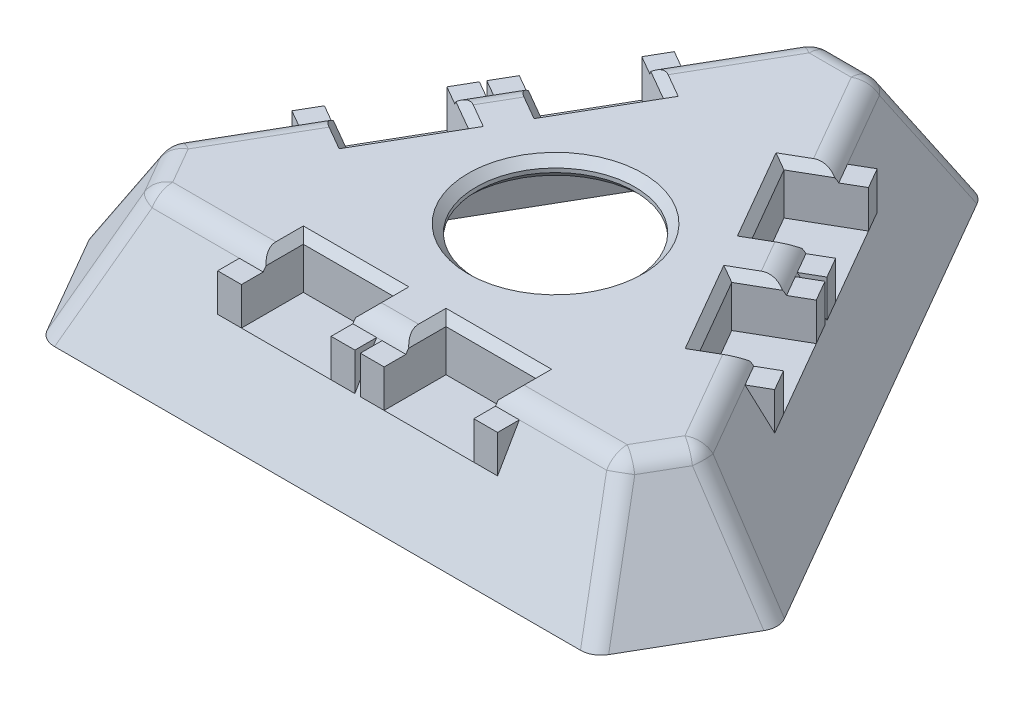
SolidWorks part; units mm, degrees
material "Epoxy, Unfilled"
ref_plane "Front Plane" through (0, 0, 0) normal (0, 0, 1) x (1, 0, 0)
ref_plane "Top Plane" through (0, 0, 0) normal (0, 1, 0) x (1, 0, 0)
ref_plane "Right Plane" through (0, 0, 0) normal (1, 0, 0) x (0, 0, -1)
sketch "Sketch1" plane through (0, 0, 0) normal (0, 1, 0) x (1, 0, 0)
  line L1 (7.32, 72.6795) -> (-7.32, 72.6795) construction
  line L5 (59.2822, -42.6788) -> (-59.2822, -42.6788) construction
  line L11 (-7.32, 72.6795) -> (-66.6024, -30.0002) construction
  line L13 (-59.2822, -42.6788) -> (-66.6024, -30.0002) construction
  line L15 (59.2822, -42.6788) -> (66.6024, -30.0002) construction
  line L16 (66.6024, -30.0002) -> (7.32, 72.6795) construction
  line L17 (69.282, -59.9993) -> (-69.2821, -59.9993)
  line L18 (-69.2821, -59.9993) -> (-86.6026, -30.0004)
  line L19 (-17.32, 90) -> (-86.6026, -30.0004)
  line L20 (17.32, 90) -> (-17.32, 90)
  line L21 (86.6025, -30.0004) -> (17.32, 90)
  line L22 (69.282, -59.9993) -> (86.6025, -30.0004)
  point P4 (0, 72.6795)
  point P6 (0, -42.6788)
  point P14 (0, 90)
  dimension "D4" = 90
  dimension "D3" = 34.64
  dimension "D1" = 138.5641
  dimension "D2" = 173.2051
  dimension "D6" = 17.3205
extrude "Boss-Extrude1" add sketch "Sketch1" along normal blind 30 draft 30
sketch "Sketch2" plane through (0, 0, 0) normal (0, -1, 0) x (1, 0, 0)
  line L10 (51.9609, 29.9993) -> (-51.9609, 29.9993)
  line L12 (51.9609, 29.9993) -> (-51.9609, 29.9993)
  line L24 (-51.9609, 29.9993) -> (0, -59.9992)
  line L25 (-51.9609, 29.9993) -> (0, -59.9992)
  line L28 (0, -59.9992) -> (51.9609, 29.9993)
  line L29 (0, -59.9992) -> (51.9609, 29.9993)
  dimension "D1" = 30
extrude "Cut-Extrude1" cut sketch "Sketch2" against normal blind 25
sketch "Sketch3" plane through (0, 0, 0) normal (0, -1, 0) x (1, 0, 0)
  line L6 (75.0555, 30.0003) -> (63.5087, 49.9993)
  line L8 (75.0555, 30.0003) -> (63.5087, 49.9993)
  line L10 (63.5087, 49.9993) -> (-63.5087, 49.9993)
  line L12 (63.5087, 49.9993) -> (-63.5087, 49.9993)
  line L14 (-63.5087, 49.9993) -> (-75.0555, 30.0003)
  line L16 (-63.5087, 49.9993) -> (-75.0555, 30.0003)
  line L24 (-75.0555, 30.0003) -> (-11.5465, -80)
  line L25 (-75.0555, 30.0003) -> (-11.5465, -80)
  line L26 (-11.5465, -80) -> (11.5465, -80)
  line L27 (-11.5465, -80) -> (11.5465, -80)
  line L28 (11.5465, -80) -> (75.0555, 30.0003)
  line L29 (11.5465, -80) -> (75.0555, 30.0003)
  dimension "D1" = 10
extrude "Cut-Extrude2" cut sketch "Sketch3" against normal offset from surface (12.5 mm away) 17.5 up to face at (0, 30, -0.0002)
ref_plane "Plane1" through (0, 0, 59.9993) normal (0, 0, 1) x (1, 0, 0)
ref_plane "Plane2" through (51.9612, 0, -29.9999) normal (0.866, 0, -0.5) x (-0.5, 0, -0.866)
ref_plane "Plane3" through (-51.9612, 0, -29.9999) normal (-0.866, 0, -0.5) x (-0.5, 0, 0.866)
sketch "Sketch7" plane through (0, 0, 59.9993) normal (0, 0, 1) x (1, 0, 0)
  line L0 (59.2822, 30) -> (66.6024, 30) construction
  line L1 (-29.2821, 30) -> (-6.6821, 30)
  line L2 (-29.2821, 30) -> (-29.2821, 17.5)
  line L3 (-29.2821, 17.5) -> (-6.6821, 17.5)
  line L4 (-6.6821, 30) -> (-6.6821, 17.5)
  line L5 (6.682, 30) -> (29.282, 30)
  line L6 (6.682, 30) -> (6.682, 17.5)
  line L7 (6.682, 17.5) -> (29.282, 17.5)
  line L8 (29.282, 30) -> (29.282, 17.5)
  dimension "D1" = 22.6
  dimension "D2" = 22.6
  dimension "D3" = 40
  dimension "D4" = 40
  dimension "D5" = 12.5
extrude "Cut-Extrude6" cut sketch "Sketch7" against normal blind 25.7036
sketch "Sketch8" plane through (-51.9612, 0, -29.9999) normal (-0.866, 0, -0.5) x (-0.5, 0, 0.866)
  line L0 (44.3419, 30) -> (51.6019, 30) construction
  line L1 (-29.2822, 30) -> (-6.6822, 30)
  line L2 (-29.2822, 30) -> (-29.2822, 17.5)
  line L3 (-29.2822, 17.5) -> (-6.6822, 17.5)
  line L4 (-6.6822, 30) -> (-6.6822, 17.5)
  line L5 (6.6825, 30) -> (29.2825, 30)
  line L6 (6.6825, 30) -> (6.6825, 17.5)
  line L7 (6.6825, 17.5) -> (29.2825, 17.5)
  line L8 (29.2825, 30) -> (29.2825, 17.5)
  dimension "D1" = 40
  dimension "D2" = 22.6
  dimension "D3" = 22.6
  dimension "D4" = 40
  dimension "D5" = 12.5
extrude "Cut-Extrude7" cut sketch "Sketch8" against normal blind 25.7
sketch "Sketch9" plane through (51.9612, 0, -29.9999) normal (0.866, 0, -0.5) x (-0.5, 0, -0.866)
  line L0 (26.3633, 30) -> (33.6201, 30) construction
  line L1 (-29.2825, 30) -> (-6.6825, 30)
  line L2 (-29.2825, 30) -> (-29.2825, 17.5)
  line L3 (-29.2825, 17.5) -> (-6.6825, 17.5)
  line L4 (-6.6825, 30) -> (-6.6825, 17.5)
  line L5 (6.6822, 30) -> (29.2822, 30)
  line L6 (6.6822, 30) -> (6.6822, 17.5)
  line L7 (6.6822, 17.5) -> (29.2822, 17.5)
  line L8 (29.2822, 30) -> (29.2822, 17.5)
  dimension "D1" = 22.6
  dimension "D2" = 22.6
  dimension "D3" = 40
  dimension "D4" = 40
  dimension "D5" = 12.5
extrude "Cut-Extrude8" cut sketch "Sketch9" against normal blind 25.7
sketch "Sketch10" plane through (0, 30, 0) normal (0, 1, 0) x (1, 0, 0)
  circle A1 centre (0, 0) radius 20
  dimension "D1" = 40
extrude "Cut-Extrude9" cut sketch "Sketch10" against normal through all
chamfer "Chamfer2" distance 2 angle 45 20 edges at (6.682, 30, 38.4872) (17.982, 30, 34.2956) (29.282, 30, 38.4872) (-29.2821, 30, 38.4872) (-17.9821, 30, 34.2956) (-6.6821, 30, 38.4872) (36.674, 30, -13.4576) (47.9741, 30, 6.1145) (38.6956, 30, -1.5766) (18.6917, 30, -44.6039) (29.9917, 30, -25.0317) (20.7133, 30, -32.7229) (-47.9741, 30, 6.1145) (-38.6956, 30, -1.5766) (-36.674, 30, -13.4576) (-29.9917, 30, -25.0317) (-20.7133, 30, -32.7229) (-18.6917, 30, -44.6039) (0, 30, 20) (0, 25, 20)
fillet "Fillet2" radius 6 18 edges at (76.6025, 15, 30.0003) (64.2821, 15, 51.339) (59.6025, 30, 17.876) (62.9423, 30, 36.3395) (45.2821, 30, 42.6788) (36.9613, 30, -21.3395) (0, 30, 42.6788) (-45.2821, 30, 42.6788) (-62.9423, 30, 36.3395) (-64.2821, 15, 51.339) (-76.6025, 15, 30.0003) (-59.6025, 30, 17.876) (-36.9613, 30, -21.3395) (-14.3201, 30, -60.5551) (14.3201, 30, -60.5551) (12.32, 15, -81.3397) (0, 30, -72.6795) (-12.32, 15, -81.3397)
ref_plane "Plane4" through (43.2112, 0, -24.9481) normal (-0.866, 0, 0.5) x (0.5, 0, 0.866)
ref_plane "Plane5" through (0, 0, 49.8956) normal (0, 0, -1) x (-1, 0, 0)
ref_plane "Plane6" through (-43.2112, 0, -24.9481) normal (0.866, 0, 0.5) x (0.5, 0, -0.866)
sketch "Sketch11" plane through (0, 0, 49.8956) normal (0, 0, -1) x (-1, 0, 0)
  line L1 (-29.282, 17.5) -> (-35.282, 17.5)
  line L2 (-29.282, 17.5) -> (-29.282, 27)
  line L3 (-29.282, 27) -> (-35.282, 27)
  line L4 (-35.282, 17.5) -> (-35.282, 27)
  line L6 (-6.682, 17.5) -> (-0.682, 17.5)
  line L7 (-6.682, 17.5) -> (-6.682, 27)
  line L8 (-6.682, 27) -> (-0.682, 27)
  line L9 (-0.682, 17.5) -> (-0.682, 27)
  line L10 (6.6821, 17.5) -> (0.6821, 17.5)
  line L11 (6.6821, 17.5) -> (6.6821, 27)
  line L12 (6.6821, 27) -> (0.6821, 27)
  line L13 (0.6821, 17.5) -> (0.6821, 27)
  line L14 (29.2821, 17.5) -> (35.2821, 17.5)
  line L15 (29.2821, 17.5) -> (29.2821, 27)
  line L16 (29.2821, 27) -> (35.2821, 27)
  line L17 (35.2821, 17.5) -> (35.2821, 27)
  line L18 (-57.2823, 27) -> (-29.282, 27) construction
  dimension "D1" = 6
  dimension "D2" = 6
  dimension "D3" = 6
  dimension "D4" = 6
extrude "Boss-Extrude2" add sketch "Sketch11" along normal up to next
sketch "Sketch12" plane through (43.2112, 0, -24.9481) normal (-0.866, 0, 0.5) x (0.5, 0, 0.866)
  line L1 (-29.2822, 17.5) -> (-35.2822, 17.5)
  line L2 (-29.2822, 17.5) -> (-29.2822, 27)
  line L3 (-29.2822, 27) -> (-35.2822, 27)
  line L4 (-35.2822, 17.5) -> (-35.2822, 27)
  line L5 (0.6825, 17.5) -> (6.6825, 17.5)
  line L6 (0.6825, 17.5) -> (0.6825, 27)
  line L7 (0.6825, 27) -> (6.6825, 27)
  line L8 (6.6825, 17.5) -> (6.6825, 27)
  line L9 (35.2825, 17.5) -> (29.2825, 17.5)
  line L10 (35.2825, 17.5) -> (35.2825, 27)
  line L11 (35.2825, 27) -> (29.2825, 27)
  line L12 (29.2825, 17.5) -> (29.2825, 27)
  line L13 (-6.6822, 17.5) -> (-0.6822, 17.5)
  line L14 (-6.6822, 17.5) -> (-6.6822, 27)
  line L15 (-6.6822, 27) -> (-0.6822, 27)
  line L16 (-0.6822, 17.5) -> (-0.6822, 27)
  line L17 (-57.2822, 27) -> (-29.2822, 27) construction
  dimension "D1" = 6
  dimension "D2" = 6
  dimension "D3" = 6
  dimension "D4" = 6
extrude "Boss-Extrude3" add sketch "Sketch12" along normal up to next
sketch "Sketch13" plane through (-43.2112, 0, -24.9481) normal (0.866, 0, 0.5) x (0.5, 0, -0.866)
  line L1 (-29.2825, 17.5) -> (-35.2825, 17.5)
  line L2 (-29.2825, 17.5) -> (-29.2825, 27)
  line L3 (-29.2825, 27) -> (-35.2825, 27)
  line L4 (-35.2825, 17.5) -> (-35.2825, 27)
  line L5 (-6.6825, 17.5) -> (-0.6825, 17.5)
  line L6 (-6.6825, 17.5) -> (-6.6825, 27)
  line L7 (-6.6825, 27) -> (-0.6825, 27)
  line L8 (-0.6825, 17.5) -> (-0.6825, 27)
  line L9 (6.6822, 17.5) -> (0.6822, 17.5)
  line L10 (6.6822, 17.5) -> (6.6822, 27)
  line L11 (6.6822, 27) -> (0.6822, 27)
  line L12 (0.6822, 17.5) -> (0.6822, 27)
  line L13 (29.2822, 17.5) -> (35.2822, 17.5)
  line L14 (29.2822, 17.5) -> (29.2822, 27)
  line L15 (29.2822, 27) -> (35.2822, 27)
  line L16 (35.2822, 17.5) -> (35.2822, 27)
  line L17 (29.2822, 27) -> (57.2822, 27) construction
  dimension "D1" = 6
  dimension "D2" = 6
  dimension "D3" = 6
  dimension "D4" = 6
extrude "Boss-Extrude4" add sketch "Sketch13" along normal up to next
